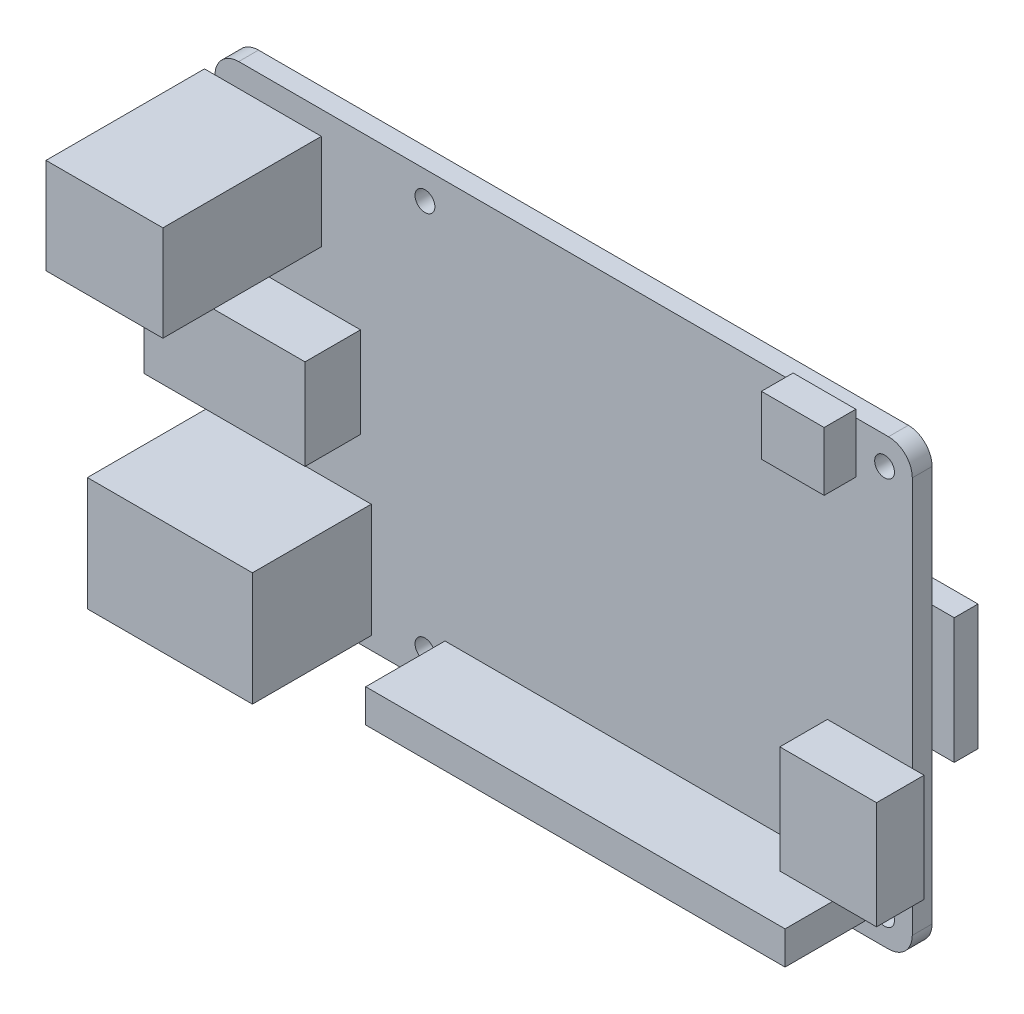
SolidWorks part; units mm, degrees
ref_plane "前视基准面" through (0, 0, 0) normal (0, 0, 1) x (1, 0, 0)
ref_plane "上视基准面" through (0, 0, 0) normal (0, 1, 0) x (1, 0, 0)
ref_plane "右视基准面" through (0, 0, 0) normal (1, 0, 0) x (0, 0, -1)
sketch "草图1" plane through (0, 0, 0) normal (0, 0, 1) x (1, 0, 0)
  line L1 (-44, -28) -> (44, -28)
  line L2 (-44, -28) -> (-44, 28)
  line L3 (-44, 28) -> (44, 28)
  line L4 (44, -28) -> (44, 28)
  line L5 (-44, -28) -> (44, 28) construction
  line L6 (-44, 28) -> (44, -28) construction
  circle A0 centre (-17.5, 24.5) radius 1.25
  circle A1 centre (40.5, 24.5) radius 1.25
  circle A2 centre (40.5, -24.5) radius 1.25
  circle A3 centre (-17.5, -24.5) radius 1.25
  point P0 (0, 0)
  point P14 (0, 0)
  point P15 (0, 0)
  point P16 (0, 0)
  point P17 (0, 0)
  point P18 (41.0214, 24.3193)
  dimension "D3" = 2.5
  dimension "D4" = 2.5
  dimension "D5" = 2.5
  dimension "D6" = 2.5
  dimension "D7" = 58
  dimension "D8" = 49
  dimension "D9" = 3.5
  dimension "D10" = 3.5
  dimension "D1" = 88
  dimension "D2" = 56
extrude "凸台-拉伸1" add sketch "草图1" along normal blind 2.5
sketch "草图3" plane through (0, 0, 2.5) normal (0, 0, 1) x (1, 0, 0)
  line L1 (-45.3211, 25.0406) -> (-30.5716, 25.0406)
  line L2 (-45.3211, 25.0406) -> (-45.3211, 12.9728)
  line L3 (-45.3211, 12.9728) -> (-30.5716, 12.9728)
  line L4 (-30.5716, 25.0406) -> (-30.5716, 12.9728)
extrude "凸台-拉伸2" add sketch "草图3" along normal blind 20
sketch "草图4" plane through (0, 0, 2.5) normal (0, 0, 1) x (1, 0, 0)
  line L1 (-45.0969, -26.3692) -> (-24.2738, -26.3692)
  line L2 (-45.0969, -26.3692) -> (-45.0969, -12.0107)
  line L3 (-45.0969, -12.0107) -> (-24.2738, -12.0107)
  line L4 (-24.2738, -26.3692) -> (-24.2738, -12.0107)
extrude "凸台-拉伸3" add sketch "草图4" along normal blind 15
sketch "草图5" plane through (0, 0, 2.5) normal (0, 0, 1) x (1, 0, 0)
  line L1 (-45.9816, 6.3626) -> (-25.6347, 6.3626)
  line L2 (-45.9816, 6.3626) -> (-45.9816, -5.0697)
  line L3 (-45.9816, -5.0697) -> (-25.6347, -5.0697)
  line L4 (-25.6347, 6.3626) -> (-25.6347, -5.0697)
extrude "凸台-拉伸4" add sketch "草图5" along normal blind 7
sketch "草图6" plane through (0, 0, 2.5) normal (0, 0, 1) x (1, 0, 0)
  line L1 (-14.9755, -22.3139) -> (37.9472, -22.3139)
  line L2 (-14.9755, -22.3139) -> (-14.9755, -26.4956)
  line L3 (-14.9755, -26.4956) -> (37.9472, -26.4956)
  line L4 (37.9472, -22.3139) -> (37.9472, -26.4956)
extrude "凸台-拉伸5" add sketch "草图6" along normal blind 10
sketch "草图7" plane through (0, 0, 2.5) normal (0, 0, 1) x (1, 0, 0)
  line L1 (45.488, -6.7524) -> (33.2856, -6.7524)
  line L2 (45.488, -6.7524) -> (45.488, -20.3259)
  line L3 (45.488, -20.3259) -> (33.2856, -20.3259)
  line L4 (33.2856, -6.7524) -> (33.2856, -20.3259)
  point P4 (33.2856, -6.7524)
extrude "凸台-拉伸6" add sketch "草图7" along normal blind 6
sketch "草图8" plane through (0, 0, 0) normal (0, 0, -1) x (-1, 0, 0)
  line L1 (-46.7915, 9.8606) -> (-22.68, 9.8606)
  line L2 (-46.7915, 9.8606) -> (-46.7915, -5.9582)
  line L3 (-46.7915, -5.9582) -> (-22.68, -5.9582)
  line L4 (-22.68, 9.8606) -> (-22.68, -5.9582)
extrude "凸台-拉伸7" add sketch "草图8" along normal blind 3
sketch "草图9" plane through (0, 0, 2.5) normal (0, 0, 1) x (1, 0, 0)
  line L1 (36.8755, 21.5219) -> (28.9594, 21.5219)
  line L2 (36.8755, 21.5219) -> (36.8755, 28.9432)
  line L3 (36.8755, 28.9432) -> (28.9594, 28.9432)
  line L4 (28.9594, 21.5219) -> (28.9594, 28.9432)
extrude "凸台-拉伸8" add sketch "草图9" along normal blind 4
fillet "圆角1" radius 3 4 edges at (-44, 28, 1.25) (44, 28, 1.25) (44, -28, 1.25) (-44, -28, 1.25)
